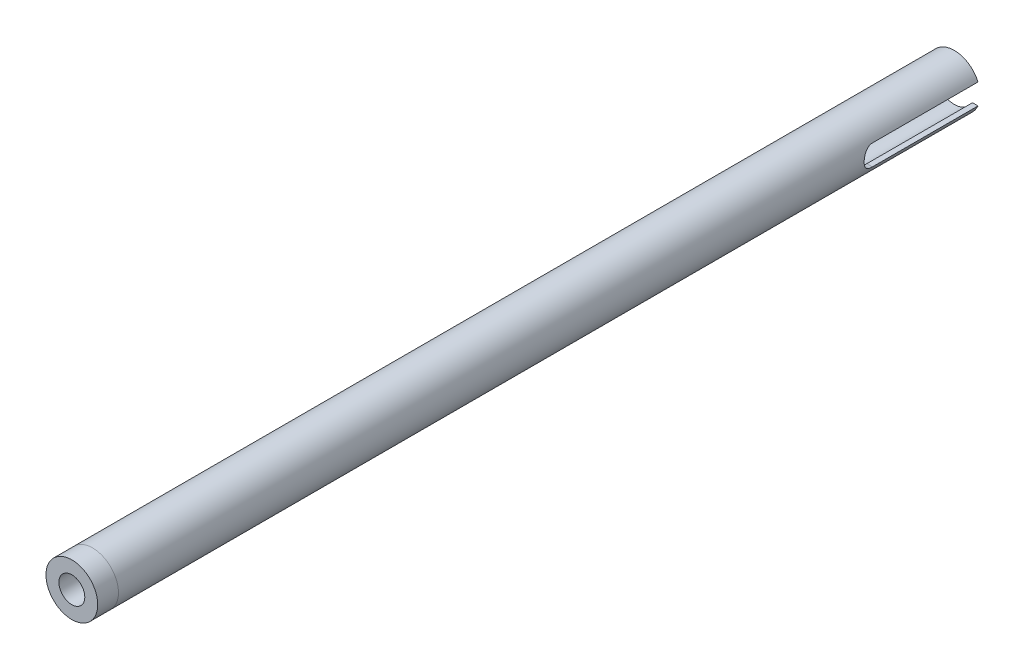
SolidWorks part; units mm, degrees
material "AISI 4130 Steel, annealed at 865C"
ref_plane "Front Plane" through (0, 0, 0) normal (0, 0, 1) x (1, 0, 0)
ref_plane "Top Plane" through (0, 0, 0) normal (0, 1, 0) x (1, 0, 0)
ref_plane "Right Plane" through (0, 0, 0) normal (1, 0, 0) x (0, 0, -1)
sketch "Axis" plane through (0, 0, 0) normal (0, 1, 0) x (1, 0, 0)
  line L0 (0, 0) -> (0, 270.5262) construction
  line L1 (0, 0) -> (0, -28.575) construction
  line L2 (0, 270.5262) -> (-7.9375, 270.5262) construction
  line L4 (0, 291.0683) -> (-10.3187, 264.3636) construction
  dimension "D1" = 28.575
  dimension "D2" = 7.9375
sketch "Sketch1" plane through (0, 0, 0) normal (0, 0, 1) x (1, 0, 0)
  line L0 (-7.9375, 0) -> (7.9375, 0) construction
  line L1 (-7.2748, 3.175) -> (7.2748, 3.175)
  line L2 (-7.2748, -3.175) -> (7.2748, -3.175)
  circle A0 centre (0, 0) radius 7.9375
  circle A1 centre (0, 0) radius 6.4135
  circle A2 centre (0, 0) radius 3.9688
  dimension "D1" = 15.875
  dimension "D3" = 7.9375
  dimension "D2" = 1.524
  dimension "D4" = 6.35
extrude "Threaded insert 1-1" add sketch "Sketch1" against normal blind 6.35 contours A2 L1 A1 | A1 L1 A0 | A2 L0 A1 L1 | A1 L0 A0 L1 | L0 A1 L2 A0 | L0 A2 L2 A1 | A2 L2 A1 | A1 L2 A0 | L0 A1 L2 A2 | L0 A0 L2 A1 | A0 L0 A1 L1 | A1 L0 A2 L1 region at (4.7887, 1.6543, 0) region at (4.7887, -1.6543, 0) region at (6.9234, 1.6163, 0) region at (6.9234, -1.6163, 0) region at (-4.7887, -1.6543, 0) region at (-4.7887, 1.6543, 0) region at (0, 4.6159, 0) region at (0, -4.6159, 0) region at (0, 6.5666, 0) region at (6.4237, -3.3281, 0) region at (-6.9234, -1.6163, 0) region at (-6.9234, 1.6163, 0)
extrude "Threaded insert 1-2" add sketch "Sketch1<3>" against normal blind 9.525 from surface contours A2 L1 A1 | A2 L0 A1 L1 | L0 A2 L2 A1 | A2 L2 A1 | L0 A1 L2 A2 | A1 L0 A2 L1 region at (4.7887, 1.6543, 0) region at (4.7887, -1.6543, 0) region at (-4.7887, -1.6543, 0) region at (-4.7887, 1.6543, 0) region at (0, 4.6159, 0) region at (0, -4.6159, 0) starting at face at (7.9375, 0, -6.35)
sketch "Sketch1<3>" plane through (0, 0, 0) normal (0, 0, 1) x (1, 0, 0) same geometry as "Sketch1"
extrude "A-arm tube" add sketch "Sketch1<4>" against normal up to vertex (270.5262 mm away) from surface separate body contours A1 L1 A0 | A1 L0 A0 L1 | L0 A1 L2 A0 | A1 L2 A0 | L0 A0 L2 A1 | A0 L0 A1 L1 region at (6.9234, 1.6163, 0) region at (6.9234, -1.6163, 0) region at (0, 6.5666, 0) region at (6.4237, -3.3281, 0) region at (-6.9234, -1.6163, 0) region at (-6.9234, 1.6163, 0) up to point (0, 0, -270.5262) starting at face at (6.4135, 0, -6.35)
sketch "Sketch1<4>" plane through (0, 0, 0) normal (0, 0, 1) x (1, 0, 0) same geometry as "Sketch1"
extrude "Apex slot" cut sketch "Sketch1<5>" along normal blind 35.56 from surface contours A0 L0 A1 L1 | L0 A0 L2 A1 | A1 L0 A0 L1 | L0 A1 L2 A0 region at (6.9234, 1.6163, 0) region at (6.9234, -1.6163, 0) region at (-6.9234, -1.6163, 0) region at (-6.9234, 1.6163, 0) starting at face at (6.4135, 0, -270.5262)
sketch "Sketch1<5>" plane through (0, 0, 0) normal (0, 0, 1) x (1, 0, 0) same geometry as "Sketch1"
fillet "Fillet1" radius 3.175 4 edges at (-6.4237, 3.175, -234.9662) (-6.4237, -3.175, -234.9662) (6.4237, -3.175, -234.9662) (6.4237, 3.175, -234.9662)
equation "\"tube diameter\"= 5 / 8"
equation "\"tube thickness\"= .06"
equation "\"apex thickness\"= .25"
equation "\"tube slot\"= 1.4"
equation "\"D1@Sketch1\"=\"tube diameter\""
equation "\"D2@Sketch1\"=\"tube thickness\""
equation "\"threaded insert hole\"= .3125"
equation "\"D3@Sketch1\"=\"threaded insert hole\""
equation "\"D4@Sketch1\"=\"apex thickness\""
equation "\"D1@Apex slot\" = \"tube slot\""
equation "\"D1@Fillet1\"=\"apex thickness\"/2"
